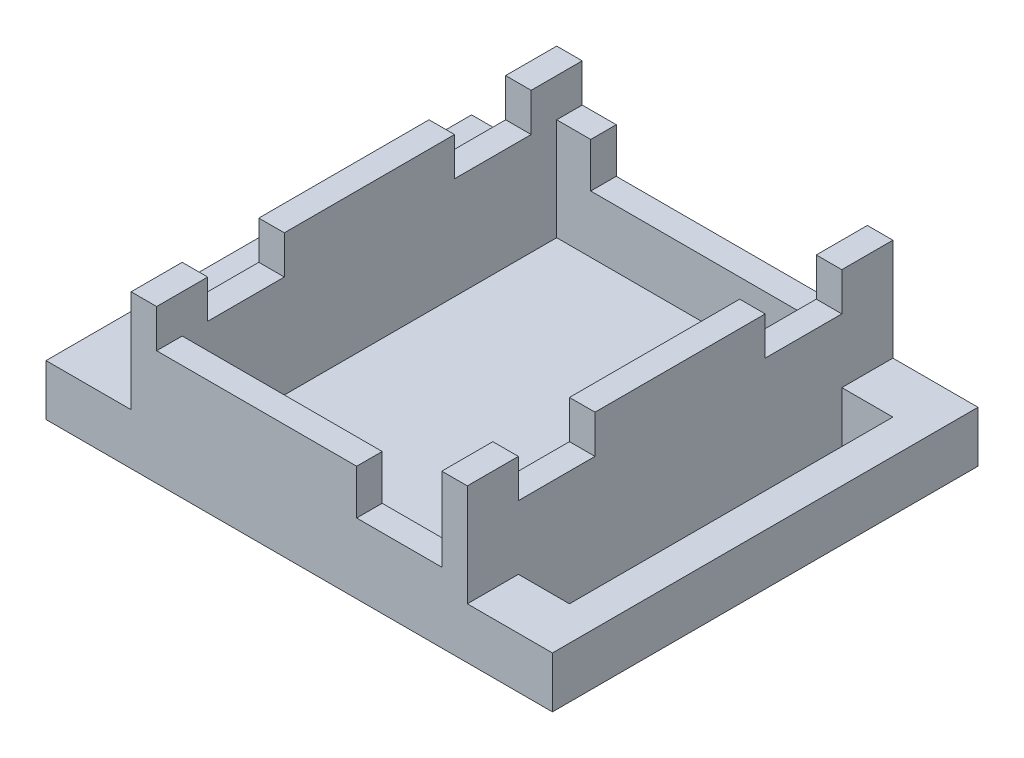
SolidWorks part; units mm, degrees
ref_plane "Front Plane" through (0, 0, 0) normal (0, 0, 1) x (1, 0, 0)
ref_plane "Top Plane" through (0, 0, 0) normal (0, 1, 0) x (1, 0, 0)
ref_plane "Right Plane" through (0, 0, 0) normal (1, 0, 0) x (0, 0, -1)
sketch "Sketch1" plane through (0, 0, 0) normal (0, 1, 0) x (1, 0, 0)
  line L1 (0, 0) -> (39.5, 0)
  line L2 (0, 0) -> (0, 50)
  line L3 (0, 50) -> (39.5, 50)
  line L4 (39.5, 0) -> (39.5, 50)
  dimension "D1" = 39.5
  dimension "D2" = 50
extrude "Boss-Extrude1" add sketch "Sketch1" along normal blind 1.5
sketch "Sketch3" plane through (0, 1.5, 0) normal (0, 1, 0) x (1, 0, 0)
  line L1 (0, 0) -> (39.5, 0)
  line L2 (0, 0) -> (0, 50)
  line L3 (0, 50) -> (39.5, 50)
  line L4 (39.5, 0) -> (39.5, 50)
  line L5 (3, 3) -> (36.5, 3)
  line L6 (3, 3) -> (3, 47)
  line L7 (3, 47) -> (36.5, 47)
  line L8 (36.5, 3) -> (36.5, 47)
  dimension "D1" = 44
  dimension "D2" = 33.5
  dimension "D3" = 3
  dimension "D4" = 3
extrude "Boss-Extrude2" add sketch "Sketch3" along normal blind 12
sketch "Sketch6" plane through (0, 0, 0) normal (0, 0, 1) x (1, 0, 0)
  line L0 (39.5, 13.5) -> (39.5, 0) construction
  line L1 (26.5, 14.23) -> (36.5, 14.23)
  line L2 (26.5, 14.23) -> (26.5, 8.23)
  line L3 (26.5, 8.23) -> (36.5, 8.23)
  line L4 (36.5, 14.23) -> (36.5, 8.23)
  line L5 (0, 0) -> (39.5, 0) construction
  point P4 (39.5, 6.75)
  dimension "D1" = 10
  dimension "D2" = 6
  dimension "D3" = 3
  dimension "D4" = 8.23
extrude "Cut-Extrude2" cut sketch "Sketch6" against normal blind 11.2
sketch "Sketch7" plane through (0, 0, -50) normal (0, 0, -1) x (-1, 0, 0)
  line L0 (-39.5, 13.5) -> (-39.5, 0) construction
  line L1 (-36.5, 14.23) -> (-7, 14.23)
  line L2 (-36.5, 14.23) -> (-36.5, 8.25)
  line L3 (-36.5, 8.25) -> (-7, 8.25)
  line L4 (-7, 14.23) -> (-7, 8.25)
  line L5 (-39.5, 0) -> (0, 0) construction
  dimension "D1" = 29.5
  dimension "D2" = 5.98
  dimension "D3" = 3
  dimension "D4" = 8.25
extrude "Cut-Extrude3" cut sketch "Sketch7" against normal blind 3.3
sketch "Sketch8" plane through (39.5, 0, 0) normal (1, 0, 0) x (0, 0, -1)
  line L1 (0, 0) -> (6, 0)
  line L2 (0, 0) -> (0, 6)
  line L3 (0, 6) -> (6, 6)
  line L4 (6, 0) -> (6, 6)
  line L5 (50, 0) -> (44, 0)
  line L6 (50, 0) -> (50, 6)
  line L7 (50, 6) -> (44, 6)
  line L8 (44, 0) -> (44, 6)
  dimension "D1" = 6
  dimension "D2" = 6
  dimension "D3" = 6
  dimension "D4" = 6
extrude "Boss-Extrude3" add sketch "Sketch8" along normal blind 10
sketch "Sketch9" plane through (0, 0, -44) normal (0, 0, 1) x (1, 0, 0)
  line L0 (49.5, 0) -> (39.5, 0) construction
  line L1 (49.5, 6) -> (45.5, 6)
  line L2 (49.5, 6) -> (49.5, 0)
  line L3 (49.5, 0) -> (45.5, 0)
  line L4 (45.5, 6) -> (45.5, 0)
  dimension "D1" = 4
extrude "Boss-Extrude4" add sketch "Sketch9" along normal blind 38
sketch "Sketch10" plane through (0, 0, 0) normal (-1, 0, 0) x (0, 0, 1)
  line L1 (-50, 0) -> (-44, 0)
  line L2 (-50, 0) -> (-50, 6)
  line L3 (-50, 6) -> (-44, 6)
  line L4 (-44, 0) -> (-44, 6)
  line L5 (0, 0) -> (-6, 0)
  line L6 (0, 0) -> (0, 6)
  line L7 (0, 6) -> (-6, 6)
  line L8 (-6, 0) -> (-6, 6)
  dimension "D1" = 6
  dimension "D2" = 6
  dimension "D3" = 6
  dimension "D4" = 6
extrude "Boss-Extrude5" add sketch "Sketch10" along normal blind 10
sketch "Sketch11" plane through (0, 0, -6) normal (0, 0, -1) x (-1, 0, 0)
  line L0 (10, 6) -> (0, 6) construction
  line L1 (10, 0) -> (6, 0)
  line L2 (10, 0) -> (10, 6)
  line L3 (10, 6) -> (6, 6)
  line L4 (6, 0) -> (6, 6)
  dimension "D1" = 4
extrude "Boss-Extrude6" add sketch "Sketch11" along normal blind 38
sketch "Sketch12" plane through (0, 13.5, 0) normal (0, 1, 0) x (1, 0, 0)
  line L0 (39.5, 0) -> (39.5, 50) construction
  line L1 (36.5, 50) -> (39.5, 50)
  line L2 (36.5, 50) -> (36.5, 44)
  line L3 (36.5, 44) -> (39.5, 44)
  line L4 (39.5, 50) -> (39.5, 44)
  line L5 (36.5, 0) -> (36.5, 50) construction
  line L6 (36.5, 35) -> (39.5, 35)
  line L7 (36.5, 35) -> (36.5, 15)
  line L8 (36.5, 15) -> (39.5, 15)
  line L9 (39.5, 35) -> (39.5, 15)
  line L10 (3, 47) -> (3, 3) construction
  line L11 (39.5, 0) -> (36.5, 0)
  line L12 (39.5, 0) -> (39.5, 6)
  line L13 (39.5, 6) -> (36.5, 6)
  line L14 (36.5, 0) -> (36.5, 6)
  line L15 (0, 50) -> (3, 50)
  line L16 (0, 50) -> (0, 44)
  line L17 (0, 44) -> (3, 44)
  line L18 (3, 50) -> (3, 44)
  line L19 (3, 47) -> (3, 3) construction
  line L20 (3, 35) -> (0, 35)
  line L21 (3, 35) -> (3, 15)
  line L22 (3, 15) -> (0, 15)
  line L23 (0, 35) -> (0, 15)
  line L24 (0, 50) -> (0, 0) construction
  line L26 (0, 0) -> (3, 0)
  line L27 (0, 0) -> (0, 6)
  line L28 (0, 6) -> (3, 6)
  line L29 (3, 0) -> (3, 6)
  dimension "D1" = 6
  dimension "D2" = 6
  dimension "D3" = 20
  dimension "D4" = 9
extrude "Boss-Extrude7" add sketch "Sketch12" along normal blind 4.5
